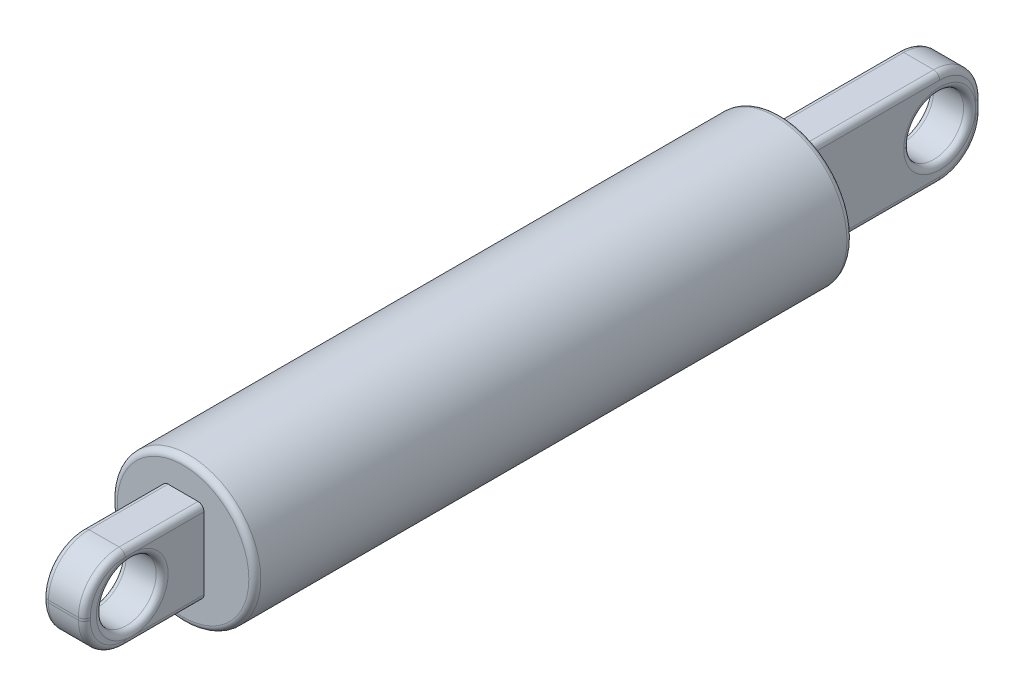
SolidWorks part; units mm, degrees
ref_plane "前基準面" through (0, 0, 0) normal (0, 0, 1) x (1, 0, 0)
ref_plane "上基準面" through (0, 0, 0) normal (0, 1, 0) x (1, 0, 0)
ref_plane "右基準面" through (0, 0, 0) normal (1, 0, 0) x (0, 0, -1)
sketch "草圖1" plane through (0, 0, 0) normal (0, 0, 1) x (1, 0, 0)
  circle A0 centre (0, 0) radius 6
extrude "填料-伸長1" add sketch "草圖1" along normal blind 50 contours A0
sketch "草圖2" plane through (0, 0, 0) normal (1, 0, 0) x (0, 0, -1)
  line L0 (11.5, 4) -> (0, 4)
  line L4 (15, 0.5) -> (15, -0.5)
  line L5 (0, 6) -> (-50, 6) construction
  line L6 (0, 0) -> (11.5, 0) construction
  line L7 (0, -6) -> (0, 6) construction
  line L8 (0, 4) -> (0, -4)
  line L9 (0, -4) -> (11.5, -4)
  line L11 (-50, -3.5) -> (-56.6, -3.5)
  line L12 (-50, -3.5) -> (-50, 3.5)
  line L13 (-50, 3.5) -> (-56.6, 3.5)
  line L14 (-60, -0.1) -> (-60, 0.1)
  line L15 (-50, -3.5) -> (-60, 3.5) construction
  line L16 (-50, 3.5) -> (-60, -3.5) construction
  line L17 (-50, 6) -> (-50, -6) construction
  line L18 (-50, 0) -> (-56, 0) construction
  circle A0 centre (11.5, 0) radius 2.5
  arc A1 (11.5, -4) -> (15, -0.5) centre (11.5, -0.5) ccw
  arc A2 (11.5, 4) -> (15, 0.5) centre (11.5, 0.5) cw
  circle A3 centre (-56, 0) radius 2.5
  arc A4 (-56.6, -3.5) -> (-60, -0.1) centre (-56.6, -0.1) cw
  arc A5 (-56.6, 3.5) -> (-60, 0.1) centre (-56.6, 0.1) ccw
  point P0 (0, 0)
  point P15 (15, -4)
  point P18 (15, 4)
  point P19 (-45, 0)
  dimension "D5" = 5
  dimension "D6" = 3.5
  dimension "D11" = 3.4
  dimension "D12" = 5
  dimension "D1" = 15
  dimension "D2" = 8
  dimension "D3" = 2
  dimension "D4" = 11.5
  dimension "D7" = 10
  dimension "D8" = 7
  dimension "D9" = 2.5
  dimension "D10" = 6
extrude "填料-伸長2" add sketch "草圖2" along normal mid plane 3.5
fillet "圓角1" radius 0.5 24 edges at (-1.75, -3.5, 53.3) (-1.75, -2.5042, 59.0042) (-1.75, 0, 60) (-1.75, 2.5042, 59.0042) (-1.75, 3.5, 53.3) (1.75, 4, -5.75) (1.75, 2.9749, -13.9749) (1.75, 0, -15) (1.75, -2.9749, -13.9749) (-1.75, -4, -5.75) (-1.75, -2.9749, -13.9749) (-1.75, 0, -15) (-1.75, 2.9749, -13.9749) (1.75, -3.5, 53.3) (1.75, -2.5042, 59.0042) (1.75, 0, 60) (1.75, 2.5042, 59.0042) (1.75, 0, -14) (1.75, -4, -5.75) (-1.75, 4, -5.75) (1.75, 0, 53.5) (1.75, 3.5, 53.3) (-1.75, 0, 53.5) (-1.75, 0, -14)
fillet "圓角3" radius 0.5 2 edges at (6, 0, 0) (6, 0, 50)
